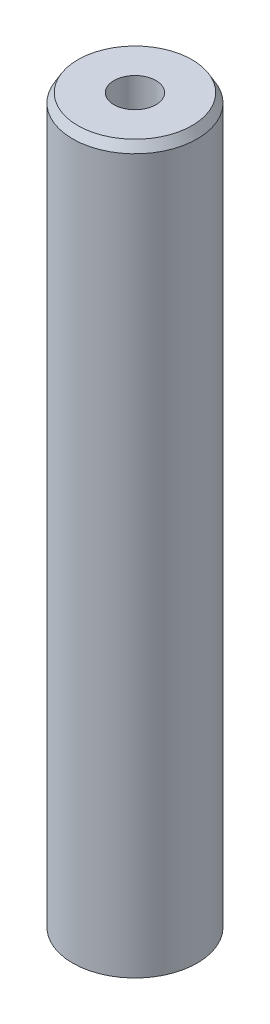
SolidWorks part; units mm, degrees
ref_plane "Front Plane" through (0, 0, 0) normal (0, 0, 1) x (1, 0, 0)
ref_plane "Top Plane" through (0, 0, 0) normal (0, 1, 0) x (1, 0, 0)
ref_plane "Right Plane" through (0, 0, 0) normal (1, 0, 0) x (0, 0, -1)
sketch "Sketch1" plane through (0, 0, 0) normal (0, 1, 0) x (1, 0, 0)
  circle A0 centre (0, 0) radius 10
  dimension "SHAFT_OD" = 20
extrude "Boss-Extrude1" add sketch "Sketch1" along normal blind 116.8681
sketch "Sketch2" plane through (0, 0, 0) normal (0, 1, 0) x (1, 0, 0)
  circle A0 centre (0, 0) radius 3.3711
  dimension "BORE_D" = 6.7423
extrude "Cut-Extrude1" cut sketch "Sketch2" along normal through all
chamfer "Chamfer1" distance 1.4383 angle 30 2 edges at (0, 116.8681, 10) (0, 0, 10) first distance on face at (0, 116.8681, 10) first distance on face at (0, 0, 3.3711)
